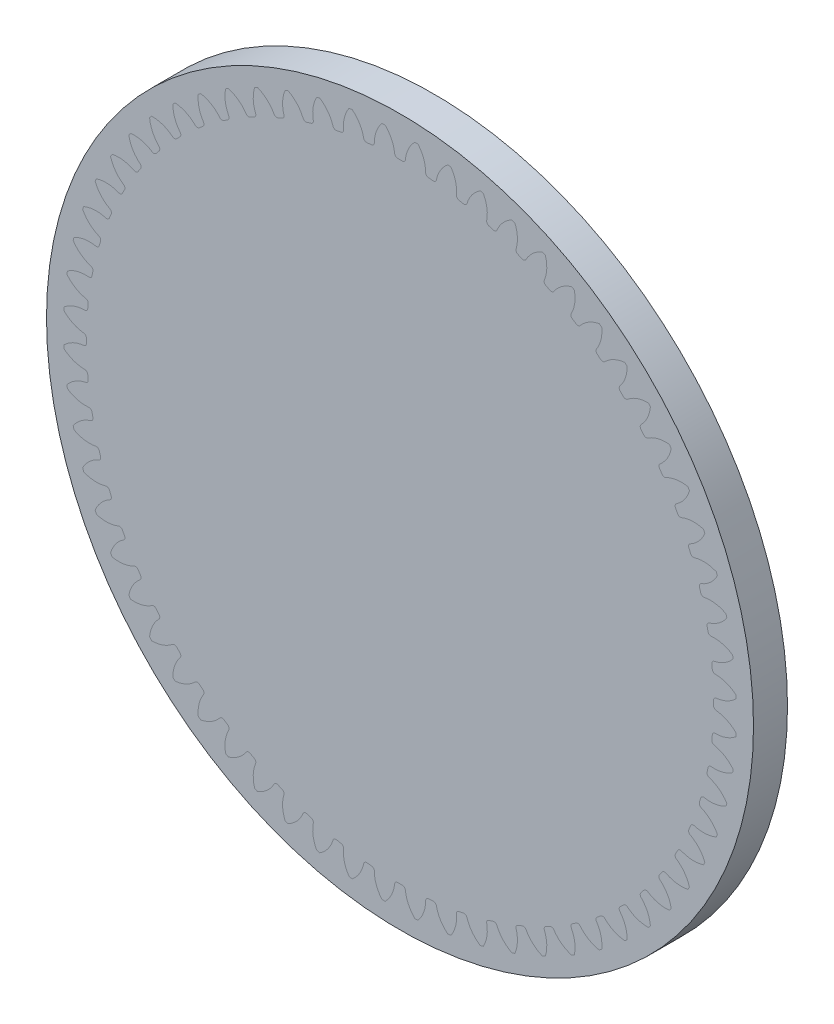
SolidWorks part; units mm, degrees
material "6061-T6 (SS)"
ref_plane "Front Plane" through (0, 0, 0) normal (0, 0, 1) x (1, 0, 0)
ref_plane "Top Plane" through (0, 0, 0) normal (0, 1, 0) x (1, 0, 0)
ref_plane "Right Plane" through (0, 0, 0) normal (1, 0, 0) x (0, 0, -1)
sketch "Sketch1" plane through (0, 0, 0) normal (0, 0, 1) x (1, 0, 0)
  circle A0 centre (0, 0) radius 96
  circle A1 centre (0, 0) radius 99
  circle A2 centre (0, 0) radius 92.25
  dimension "D1" = 192
  dimension "D2" = 198
  dimension "D3" = 6.75
extrude "Boss-Extrude1" add sketch "Sketch1" along normal mid plane 10 contours A1
sketch "Sketch2" plane through (0, 0, 0) normal (0, 0, 1) x (1, 0, 0)
  line L0 (0, 0) -> (0, 99) construction
  line L1 (-2.356, 95.9711) -> (2.356, 95.9711) construction
  line L2 (-1.5299, 92.2373) -> (0, 0) construction
  line L3 (0, 90.6795) -> (-4.1121, 99.9154) construction
  line L4 (0, 0) -> (4.8577, 98.8808) construction
  line L5 (2.356, 95.9711) -> (7.0622, 95.7399) construction
  circle A0 centre (0, 0) radius 99 construction
  arc A1 (-5.511, 99.848) -> (-1.5299, 92.2373) centre (-11.0986, 92.0786) cw
  arc A2 (5.511, 99.848) -> (1.5299, 92.2373) centre (11.0986, 92.0786) ccw
  circle A3 centre (0, 0) radius 92.25 construction
  arc A4 (1.5299, 92.2373) -> (-1.5299, 92.2373) centre (0, 0) ccw
  circle A6 centre (0, 0) radius 96 construction
  circle A7 centre (0, 0) radius 100
  arc A8 (5.511, 99.848) -> (-5.511, 99.848) centre (0, 0) ccw
  circle A9 centre (0, 0) radius 99 construction
  dimension "D2" = 24
  dimension "D3" = 2.813
extrude "Cut-Extrude1" cut sketch "Sketch2" against normal through all both and the other way through all
fillet "Fillet1" radius 0.9 2 edges at (1.5299, 92.2373, 0) (-1.5299, 92.2373, 0)
pattern_circular "CirPattern1" count 64 over 360 about axis through (0, 0, 5) along (0, 0, 1) of "Cut-Extrude1", "Fillet1"
sketch "Sketch3" plane through (0, 0, 0) normal (0, 0, 1) x (1, 0, 0)
  circle A3 centre (0, 0) radius 104
  circle A4 centre (0, 0) radius 104
  arc A388 (-5.3262, 98.8566) -> (-7.5501, 92.7623) centre (2.0199, 92.7231) ccw
  arc A389 (-8.3684, 91.8696) -> (-7.5501, 92.7623) centre (-8.4501, 92.7659) ccw
  arc A390 (-8.3684, 91.8696) -> (-9.7153, 91.737) centre (0, 0) ccw
  arc A391 (-10.692, 92.4528) -> (-9.7153, 91.737) centre (-9.8101, 92.632) ccw
  arc A392 (-10.692, 92.4528) -> (-14.0621, 97.9962) centre (-20.0705, 90.5474) ccw
  arc A393 (-14.0621, 97.9962) -> (-14.9902, 97.8585) centre (0, 0) ccw
  arc A394 (-14.9902, 97.8585) -> (-16.606, 91.5755) centre (-7.0783, 92.4746) ccw
  arc A395 (-17.3329, 90.607) -> (-16.606, 91.5755) centre (-17.502, 91.491) ccw
  arc A396 (-17.3329, 90.607) -> (-18.6603, 90.343) centre (0, 0) ccw
  arc A397 (-19.7025, 90.9596) -> (-18.6603, 90.343) centre (-18.8423, 91.2244) ccw
  arc A398 (-19.7025, 90.9596) -> (-23.5997, 96.146) centre (-28.849, 88.1441) ccw
  arc A399 (-23.5997, 96.146) -> (-24.5098, 95.918) centre (0, 0) ccw
  arc A400 (-24.5098, 95.918) -> (-25.502, 89.5069) centre (-16.1083, 91.3355) ccw
  arc A401 (-26.1305, 88.4718) -> (-25.502, 89.5069) centre (-26.3854, 89.3349) ccw
  arc A402 (-26.1305, 88.4718) -> (-27.4256, 88.0789) centre (0, 0) ccw
  arc A403 (-28.5232, 88.5904) -> (-27.4256, 88.0789) centre (-27.6932, 88.9382) ccw
  arc A404 (-28.5232, 88.5904) -> (-32.91, 93.3699) centre (-37.3497, 84.892) ccw
  arc A405 (-32.91, 93.3699) -> (-33.7934, 93.0538) centre (0, 0) ccw
  arc A406 (-33.7934, 93.0538) -> (-34.1524, 86.5763) centre (-24.9832, 89.3168) ccw
  arc A407 (-34.6764, 85.4846) -> (-34.1524, 86.5763) centre (-35.0147, 86.3185) ccw
  arc A408 (-34.6764, 85.4846) -> (-35.9268, 84.9666) centre (0, 0) ccw
  arc A409 (-37.0693, 85.3681) -> (-35.9268, 84.9666) centre (-36.2773, 85.7956) ccw
  arc A410 (-37.0693, 85.3681) -> (-41.9034, 89.6945) centre (-45.4907, 80.8223) ccw
  arc A411 (-41.9034, 89.6945) -> (-42.7516, 89.2934) centre (0, 0) ccw
  arc A412 (-42.7516, 89.2934) -> (-42.4739, 82.8119) centre (-33.6174, 86.4379) ccw
  arc A413 (-42.8884, 81.674) -> (-42.4739, 82.8119) centre (-43.3068, 82.4709) ccw
  arc A414 (-42.8884, 81.674) -> (-44.082, 81.0361) centre (0, 0) ccw
  arc A415 (-45.2583, 81.3236) -> (-44.082, 81.0361) centre (-44.512, 81.8267) ccw
  arc A416 (-45.2583, 81.3236) -> (-50.4932, 85.1554) centre (-53.1937, 75.9742) ccw
  arc A417 (-50.4932, 85.1554) -> (-51.298, 84.673) centre (0, 0) ccw
  arc A418 (-51.298, 84.673) -> (-50.3864, 78.2499) centre (-41.928, 82.7266) ccw
  arc A419 (-50.6873, 77.077) -> (-50.3864, 78.2499) centre (-51.1818, 77.8289) ccw
  arc A420 (-50.6873, 77.077) -> (-51.8126, 76.3251) centre (0, 0) ccw
  arc A421 (-53.0115, 76.4959) -> (-51.8126, 76.3251) centre (-52.3181, 77.0697) ccw
  arc A422 (-53.0115, 76.4959) -> (-58.5968, 79.7961) centre (-60.3843, 70.3945) ccw
  arc A423 (-58.5968, 79.7961) -> (-59.3504, 79.2372) centre (0, 0) ccw
  arc A424 (-59.3504, 79.2372) -> (-57.8136, 72.9344) centre (-49.8347, 78.2186) ccw
  arc A425 (-57.9981, 71.7376) -> (-57.8136, 72.9344) centre (-58.564, 72.4375) ccw
  arc A426 (-57.9981, 71.7376) -> (-59.0443, 70.879) centre (0, 0) ccw
  arc A427 (-60.2541, 70.9315) -> (-59.0443, 70.879) centre (-59.6203, 71.5705) ccw
  arc A428 (-60.2541, 70.9315) -> (-66.136, 73.6684) centre (-66.9934, 64.1368) ccw
  arc A429 (-66.136, 73.6684) -> (-66.8312, 73.0383) centre (0, 0) ccw
  arc A430 (-66.8312, 73.0383) -> (-64.684, 66.9165) centre (-57.2615, 72.9573) ccw
  arc A431 (-64.7504, 65.7073) -> (-64.684, 66.9165) centre (-65.3821, 66.3484) ccw
  arc A432 (-64.7504, 65.7073) -> (-65.7073, 64.7504) centre (0, 0) ccw
  arc A433 (-66.9165, 64.684) -> (-65.7073, 64.7504) centre (-66.3484, 65.3821) ccw
  arc A434 (-66.9165, 64.684) -> (-73.0383, 66.8312) centre (-72.9573, 57.2615) ccw
  arc A435 (-73.0383, 66.8312) -> (-73.6684, 66.136) centre (0, 0) ccw
  arc A436 (-73.6684, 66.136) -> (-70.9315, 60.2541) centre (-64.1368, 66.9934) ccw
  arc A437 (-70.879, 59.0443) -> (-70.9315, 60.2541) centre (-71.5705, 59.6203) ccw
  arc A438 (-70.879, 59.0443) -> (-71.7376, 57.9981) centre (0, 0) ccw
  arc A439 (-72.9344, 57.8136) -> (-71.7376, 57.9981) centre (-72.4375, 58.564) ccw
  arc A440 (-72.9344, 57.8136) -> (-79.2372, 59.3504) centre (-78.2186, 49.8347) ccw
  arc A441 (-79.2372, 59.3504) -> (-79.7961, 58.5968) centre (0, 0) ccw
  arc A442 (-79.7961, 58.5968) -> (-76.4959, 53.0115) centre (-70.3945, 60.3843) ccw
  arc A443 (-76.3251, 51.8126) -> (-76.4959, 53.0115) centre (-77.0697, 52.3181) ccw
  arc A444 (-76.3251, 51.8126) -> (-77.077, 50.6873) centre (0, 0) ccw
  arc A445 (-78.2499, 50.3864) -> (-77.077, 50.6873) centre (-77.8289, 51.1818) ccw
  arc A446 (-78.2499, 50.3864) -> (-84.673, 51.298) centre (-82.7266, 41.928) ccw
  arc A447 (-84.673, 51.298) -> (-85.1554, 50.4932) centre (0, 0) ccw
  arc A448 (-85.1554, 50.4932) -> (-81.3236, 45.2583) centre (-75.9742, 53.1937) ccw
  arc A449 (-81.0361, 44.082) -> (-81.3236, 45.2583) centre (-81.8267, 44.512) ccw
  arc A450 (-81.0361, 44.082) -> (-81.674, 42.8884) centre (0, 0) ccw
  arc A451 (-82.8119, 42.4739) -> (-81.674, 42.8884) centre (-82.4709, 43.3068) ccw
  arc A452 (-82.8119, 42.4739) -> (-89.2934, 42.7516) centre (-86.4379, 33.6174) ccw
  arc A453 (-89.2934, 42.7516) -> (-89.6945, 41.9034) centre (0, 0) ccw
  arc A454 (-89.6945, 41.9034) -> (-85.3681, 37.0693) centre (-80.8223, 45.4907) ccw
  arc A455 (-84.9666, 35.9268) -> (-85.3681, 37.0693) centre (-85.7956, 36.2773) ccw
  arc A456 (-84.9666, 35.9268) -> (-85.4846, 34.6764) centre (0, 0) ccw
  arc A457 (-86.5763, 34.1524) -> (-85.4846, 34.6764) centre (-86.3185, 35.0147) ccw
  arc A458 (-86.5763, 34.1524) -> (-93.0538, 33.7934) centre (-89.3168, 24.9832) ccw
  arc A459 (-93.0538, 33.7934) -> (-93.3699, 32.91) centre (0, 0) ccw
  arc A460 (-93.3699, 32.91) -> (-88.5904, 28.5232) centre (-84.892, 37.3497) ccw
  arc A461 (-88.0789, 27.4256) -> (-88.5904, 28.5232) centre (-88.9382, 27.6932) ccw
  arc A462 (-88.0789, 27.4256) -> (-88.4718, 26.1305) centre (0, 0) ccw
  arc A463 (-89.5069, 25.502) -> (-88.4718, 26.1305) centre (-89.3349, 26.3854) ccw
  arc A464 (-89.5069, 25.502) -> (-95.918, 24.5098) centre (-91.3355, 16.1083) ccw
  arc A465 (-95.918, 24.5098) -> (-96.146, 23.5997) centre (0, 0) ccw
  arc A466 (-96.146, 23.5997) -> (-90.9596, 19.7025) centre (-88.1441, 28.849) ccw
  arc A467 (-90.343, 18.6603) -> (-90.9596, 19.7025) centre (-91.2244, 18.8423) ccw
  arc A468 (-90.343, 18.6603) -> (-90.607, 17.3329) centre (0, 0) ccw
  arc A469 (-91.5755, 16.606) -> (-90.607, 17.3329) centre (-91.491, 17.502) ccw
  arc A470 (-91.5755, 16.606) -> (-97.8585, 14.9902) centre (-92.4746, 7.0783) ccw
  arc A471 (-97.8585, 14.9902) -> (-97.9962, 14.0621) centre (0, 0) ccw
  arc A472 (-97.9962, 14.0621) -> (-92.4528, 10.692) centre (-90.5474, 20.0705) ccw
  arc A473 (-91.737, 9.7153) -> (-92.4528, 10.692) centre (-92.632, 9.8101) ccw
  arc A474 (-91.737, 9.7153) -> (-91.8696, 8.3684) centre (0, 0) ccw
  arc A475 (-92.7623, 7.5501) -> (-91.8696, 8.3684) centre (-92.7659, 8.4501) ccw
  arc A476 (-92.7623, 7.5501) -> (-98.8566, 5.3262) centre (-92.7231, -2.0199) ccw
  arc A477 (-98.8566, 5.3262) -> (-98.9027, 4.3891) centre (0, 0) ccw
  arc A478 (-98.9027, 4.3891) -> (-93.0556, 1.5786) centre (-92.0786, 11.0986) ccw
  arc A479 (-92.2475, 0.6767) -> (-93.0556, 1.5786) centre (-93.1475, 0.6833) ccw
  arc A480 (-92.2475, 0.6767) -> (-92.2475, -0.6767) centre (0, 0) ccw
  arc A481 (-93.0556, -1.5786) -> (-92.2475, -0.6767) centre (-93.1475, -0.6833) ccw
  arc A482 (-93.0556, -1.5786) -> (-98.9027, -4.3891) centre (-92.0786, -11.0986) ccw
  arc A483 (-98.9027, -4.3891) -> (-98.8566, -5.3262) centre (0, 0) ccw
  arc A484 (-98.8566, -5.3262) -> (-92.7623, -7.5501) centre (-92.7231, 2.0199) ccw
  arc A485 (-91.8696, -8.3684) -> (-92.7623, -7.5501) centre (-92.7659, -8.4501) ccw
  arc A486 (-91.8696, -8.3684) -> (-91.737, -9.7153) centre (0, 0) ccw
  arc A487 (-92.4528, -10.692) -> (-91.737, -9.7153) centre (-92.632, -9.8101) ccw
  arc A488 (-92.4528, -10.692) -> (-97.9962, -14.0621) centre (-90.5474, -20.0705) ccw
  arc A489 (-97.9962, -14.0621) -> (-97.8585, -14.9902) centre (0, 0) ccw
  arc A490 (-97.8585, -14.9902) -> (-91.5755, -16.606) centre (-92.4746, -7.0783) ccw
  arc A491 (-90.607, -17.3329) -> (-91.5755, -16.606) centre (-91.491, -17.502) ccw
  arc A492 (-90.607, -17.3329) -> (-90.343, -18.6603) centre (0, 0) ccw
  arc A493 (-90.9596, -19.7025) -> (-90.343, -18.6603) centre (-91.2244, -18.8423) ccw
  arc A494 (-90.9596, -19.7025) -> (-96.146, -23.5997) centre (-88.1441, -28.849) ccw
  arc A495 (-96.146, -23.5997) -> (-95.918, -24.5098) centre (0, 0) ccw
  arc A496 (-95.918, -24.5098) -> (-89.5069, -25.502) centre (-91.3355, -16.1083) ccw
  arc A497 (-88.4718, -26.1305) -> (-89.5069, -25.502) centre (-89.3349, -26.3854) ccw
  arc A498 (-88.4718, -26.1305) -> (-88.0789, -27.4256) centre (0, 0) ccw
  arc A499 (-88.5904, -28.5232) -> (-88.0789, -27.4256) centre (-88.9382, -27.6932) ccw
  arc A500 (-88.5904, -28.5232) -> (-93.3699, -32.91) centre (-84.892, -37.3497) ccw
  arc A501 (-93.3699, -32.91) -> (-93.0538, -33.7934) centre (0, 0) ccw
  arc A502 (-93.0538, -33.7934) -> (-86.5763, -34.1524) centre (-89.3168, -24.9832) ccw
  arc A503 (-85.4846, -34.6764) -> (-86.5763, -34.1524) centre (-86.3185, -35.0147) ccw
  arc A504 (-85.4846, -34.6764) -> (-84.9666, -35.9268) centre (0, 0) ccw
  arc A505 (-85.3681, -37.0693) -> (-84.9666, -35.9268) centre (-85.7956, -36.2773) ccw
  arc A506 (-85.3681, -37.0693) -> (-89.6945, -41.9034) centre (-80.8223, -45.4907) ccw
  arc A507 (-89.6945, -41.9034) -> (-89.2934, -42.7516) centre (0, 0) ccw
  arc A508 (-89.2934, -42.7516) -> (-82.8119, -42.4739) centre (-86.4379, -33.6174) ccw
  arc A509 (-81.674, -42.8884) -> (-82.8119, -42.4739) centre (-82.4709, -43.3068) ccw
  arc A510 (-81.674, -42.8884) -> (-81.0361, -44.082) centre (0, 0) ccw
  arc A511 (-81.3236, -45.2583) -> (-81.0361, -44.082) centre (-81.8267, -44.512) ccw
  arc A512 (-81.3236, -45.2583) -> (-85.1554, -50.4932) centre (-75.9742, -53.1937) ccw
  arc A513 (-85.1554, -50.4932) -> (-84.673, -51.298) centre (0, 0) ccw
  arc A514 (-84.673, -51.298) -> (-78.2499, -50.3864) centre (-82.7266, -41.928) ccw
  arc A515 (-77.077, -50.6873) -> (-78.2499, -50.3864) centre (-77.8289, -51.1818) ccw
  arc A516 (-77.077, -50.6873) -> (-76.3251, -51.8126) centre (0, 0) ccw
  arc A517 (-76.4959, -53.0115) -> (-76.3251, -51.8126) centre (-77.0697, -52.3181) ccw
  arc A518 (-76.4959, -53.0115) -> (-79.7961, -58.5968) centre (-70.3945, -60.3843) ccw
  arc A519 (-79.7961, -58.5968) -> (-79.2372, -59.3504) centre (0, 0) ccw
  arc A520 (-79.2372, -59.3504) -> (-72.9344, -57.8136) centre (-78.2186, -49.8347) ccw
  arc A521 (-71.7376, -57.9981) -> (-72.9344, -57.8136) centre (-72.4375, -58.564) ccw
  arc A522 (-71.7376, -57.9981) -> (-70.879, -59.0443) centre (0, 0) ccw
  arc A523 (-70.9315, -60.2541) -> (-70.879, -59.0443) centre (-71.5705, -59.6203) ccw
  arc A524 (-70.9315, -60.2541) -> (-73.6684, -66.136) centre (-64.1368, -66.9934) ccw
  arc A525 (-73.6684, -66.136) -> (-73.0383, -66.8312) centre (0, 0) ccw
  arc A526 (-73.0383, -66.8312) -> (-66.9165, -64.684) centre (-72.9573, -57.2615) ccw
  arc A527 (-65.7073, -64.7504) -> (-66.9165, -64.684) centre (-66.3484, -65.3821) ccw
  arc A528 (-65.7073, -64.7504) -> (-64.7504, -65.7073) centre (0, 0) ccw
  arc A529 (-64.684, -66.9165) -> (-64.7504, -65.7073) centre (-65.3821, -66.3484) ccw
  arc A530 (-64.684, -66.9165) -> (-66.8312, -73.0383) centre (-57.2615, -72.9573) ccw
  arc A531 (-66.8312, -73.0383) -> (-66.136, -73.6684) centre (0, 0) ccw
  arc A532 (-66.136, -73.6684) -> (-60.2541, -70.9315) centre (-66.9934, -64.1368) ccw
  arc A533 (-59.0443, -70.879) -> (-60.2541, -70.9315) centre (-59.6203, -71.5705) ccw
  arc A534 (-59.0443, -70.879) -> (-57.9981, -71.7376) centre (0, 0) ccw
  arc A535 (-57.8136, -72.9344) -> (-57.9981, -71.7376) centre (-58.564, -72.4375) ccw
  arc A536 (-57.8136, -72.9344) -> (-59.3504, -79.2372) centre (-49.8347, -78.2186) ccw
  arc A537 (-59.3504, -79.2372) -> (-58.5968, -79.7961) centre (0, 0) ccw
  arc A538 (-58.5968, -79.7961) -> (-53.0115, -76.4959) centre (-60.3843, -70.3945) ccw
  arc A539 (-51.8126, -76.3251) -> (-53.0115, -76.4959) centre (-52.3181, -77.0697) ccw
  arc A540 (-51.8126, -76.3251) -> (-50.6873, -77.077) centre (0, 0) ccw
  arc A541 (-50.3864, -78.2499) -> (-50.6873, -77.077) centre (-51.1818, -77.8289) ccw
  arc A542 (-50.3864, -78.2499) -> (-51.298, -84.673) centre (-41.928, -82.7266) ccw
  arc A543 (-51.298, -84.673) -> (-50.4932, -85.1554) centre (0, 0) ccw
  arc A544 (-50.4932, -85.1554) -> (-45.2583, -81.3236) centre (-53.1937, -75.9742) ccw
  arc A545 (-44.082, -81.0361) -> (-45.2583, -81.3236) centre (-44.512, -81.8267) ccw
  arc A546 (-44.082, -81.0361) -> (-42.8884, -81.674) centre (0, 0) ccw
  arc A547 (-42.4739, -82.8119) -> (-42.8884, -81.674) centre (-43.3068, -82.4709) ccw
  arc A548 (-42.4739, -82.8119) -> (-42.7516, -89.2934) centre (-33.6174, -86.4379) ccw
  arc A549 (-42.7516, -89.2934) -> (-41.9034, -89.6945) centre (0, 0) ccw
  arc A550 (-41.9034, -89.6945) -> (-37.0693, -85.3681) centre (-45.4907, -80.8223) ccw
  arc A551 (-35.9268, -84.9666) -> (-37.0693, -85.3681) centre (-36.2773, -85.7956) ccw
  arc A552 (-35.9268, -84.9666) -> (-34.6764, -85.4846) centre (0, 0) ccw
  arc A553 (-34.1524, -86.5763) -> (-34.6764, -85.4846) centre (-35.0147, -86.3185) ccw
  arc A554 (-34.1524, -86.5763) -> (-33.7934, -93.0538) centre (-24.9832, -89.3168) ccw
  arc A555 (-33.7934, -93.0538) -> (-32.91, -93.3699) centre (0, 0) ccw
  arc A556 (-32.91, -93.3699) -> (-28.5232, -88.5904) centre (-37.3497, -84.892) ccw
  arc A557 (-27.4256, -88.0789) -> (-28.5232, -88.5904) centre (-27.6932, -88.9382) ccw
  arc A558 (-27.4256, -88.0789) -> (-26.1305, -88.4718) centre (0, 0) ccw
  arc A559 (-25.502, -89.5069) -> (-26.1305, -88.4718) centre (-26.3854, -89.3349) ccw
  arc A560 (-25.502, -89.5069) -> (-24.5098, -95.918) centre (-16.1083, -91.3355) ccw
  arc A561 (-24.5098, -95.918) -> (-23.5997, -96.146) centre (0, 0) ccw
  arc A562 (-23.5997, -96.146) -> (-19.7025, -90.9596) centre (-28.849, -88.1441) ccw
  arc A563 (-18.6603, -90.343) -> (-19.7025, -90.9596) centre (-18.8423, -91.2244) ccw
  arc A564 (-18.6603, -90.343) -> (-17.3329, -90.607) centre (0, 0) ccw
  arc A565 (-16.606, -91.5755) -> (-17.3329, -90.607) centre (-17.502, -91.491) ccw
  arc A566 (-16.606, -91.5755) -> (-14.9902, -97.8585) centre (-7.0783, -92.4746) ccw
  arc A567 (-14.9902, -97.8585) -> (-14.0621, -97.9962) centre (0, 0) ccw
  arc A568 (-14.0621, -97.9962) -> (-10.692, -92.4528) centre (-20.0705, -90.5474) ccw
  arc A569 (-9.7153, -91.737) -> (-10.692, -92.4528) centre (-9.8101, -92.632) ccw
  arc A570 (-9.7153, -91.737) -> (-8.3684, -91.8696) centre (0, 0) ccw
  arc A571 (-7.5501, -92.7623) -> (-8.3684, -91.8696) centre (-8.4501, -92.7659) ccw
  arc A572 (-7.5501, -92.7623) -> (-5.3262, -98.8566) centre (2.0199, -92.7231) ccw
  arc A573 (-5.3262, -98.8566) -> (-4.3891, -98.9027) centre (0, 0) ccw
  arc A574 (-4.3891, -98.9027) -> (-1.5786, -93.0556) centre (-11.0986, -92.0786) ccw
  arc A575 (-0.6767, -92.2475) -> (-1.5786, -93.0556) centre (-0.6833, -93.1475) ccw
  arc A576 (-0.6767, -92.2475) -> (0.6767, -92.2475) centre (0, 0) ccw
  arc A577 (1.5786, -93.0556) -> (0.6767, -92.2475) centre (0.6833, -93.1475) ccw
  arc A578 (1.5786, -93.0556) -> (4.3891, -98.9027) centre (11.0986, -92.0786) ccw
  arc A579 (4.3891, -98.9027) -> (5.3262, -98.8566) centre (0, 0) ccw
  arc A580 (5.3262, -98.8566) -> (7.5501, -92.7623) centre (-2.0199, -92.7231) ccw
  arc A581 (8.3684, -91.8696) -> (7.5501, -92.7623) centre (8.4501, -92.7659) ccw
  arc A582 (8.3684, -91.8696) -> (9.7153, -91.737) centre (0, 0) ccw
  arc A583 (10.692, -92.4528) -> (9.7153, -91.737) centre (9.8101, -92.632) ccw
  arc A584 (10.692, -92.4528) -> (14.0621, -97.9962) centre (20.0705, -90.5474) ccw
  arc A585 (14.0621, -97.9962) -> (14.9902, -97.8585) centre (0, 0) ccw
  arc A586 (14.9902, -97.8585) -> (16.606, -91.5755) centre (7.0783, -92.4746) ccw
  arc A587 (17.3329, -90.607) -> (16.606, -91.5755) centre (17.502, -91.491) ccw
  arc A588 (17.3329, -90.607) -> (18.6603, -90.343) centre (0, 0) ccw
  arc A589 (19.7025, -90.9596) -> (18.6603, -90.343) centre (18.8423, -91.2244) ccw
  arc A590 (19.7025, -90.9596) -> (23.5997, -96.146) centre (28.849, -88.1441) ccw
  arc A591 (23.5997, -96.146) -> (24.5098, -95.918) centre (0, 0) ccw
  arc A592 (24.5098, -95.918) -> (25.502, -89.5069) centre (16.1083, -91.3355) ccw
  arc A593 (26.1305, -88.4718) -> (25.502, -89.5069) centre (26.3854, -89.3349) ccw
  arc A594 (26.1305, -88.4718) -> (27.4256, -88.0789) centre (0, 0) ccw
  arc A595 (28.5232, -88.5904) -> (27.4256, -88.0789) centre (27.6932, -88.9382) ccw
  arc A596 (28.5232, -88.5904) -> (32.91, -93.3699) centre (37.3497, -84.892) ccw
  arc A597 (32.91, -93.3699) -> (33.7934, -93.0538) centre (0, 0) ccw
  arc A598 (33.7934, -93.0538) -> (34.1524, -86.5763) centre (24.9832, -89.3168) ccw
  arc A599 (34.6764, -85.4846) -> (34.1524, -86.5763) centre (35.0147, -86.3185) ccw
  arc A600 (34.6764, -85.4846) -> (35.9268, -84.9666) centre (0, 0) ccw
  arc A601 (37.0693, -85.3681) -> (35.9268, -84.9666) centre (36.2773, -85.7956) ccw
  arc A602 (37.0693, -85.3681) -> (41.9034, -89.6945) centre (45.4907, -80.8223) ccw
  arc A603 (41.9034, -89.6945) -> (42.7516, -89.2934) centre (0, 0) ccw
  arc A604 (42.7516, -89.2934) -> (42.4739, -82.8119) centre (33.6174, -86.4379) ccw
  arc A605 (42.8884, -81.674) -> (42.4739, -82.8119) centre (43.3068, -82.4709) ccw
  arc A606 (42.8884, -81.674) -> (44.082, -81.0361) centre (0, 0) ccw
  arc A607 (45.2583, -81.3236) -> (44.082, -81.0361) centre (44.512, -81.8267) ccw
  arc A608 (45.2583, -81.3236) -> (50.4932, -85.1554) centre (53.1937, -75.9742) ccw
  arc A609 (50.4932, -85.1554) -> (51.298, -84.673) centre (0, 0) ccw
  arc A610 (51.298, -84.673) -> (50.3864, -78.2499) centre (41.928, -82.7266) ccw
  arc A611 (50.6873, -77.077) -> (50.3864, -78.2499) centre (51.1818, -77.8289) ccw
  arc A612 (50.6873, -77.077) -> (51.8126, -76.3251) centre (0, 0) ccw
  arc A613 (53.0115, -76.4959) -> (51.8126, -76.3251) centre (52.3181, -77.0697) ccw
  arc A614 (53.0115, -76.4959) -> (58.5968, -79.7961) centre (60.3843, -70.3945) ccw
  arc A615 (58.5968, -79.7961) -> (59.3504, -79.2372) centre (0, 0) ccw
  arc A616 (59.3504, -79.2372) -> (57.8136, -72.9344) centre (49.8347, -78.2186) ccw
  arc A617 (57.9981, -71.7376) -> (57.8136, -72.9344) centre (58.564, -72.4375) ccw
  arc A618 (57.9981, -71.7376) -> (59.0443, -70.879) centre (0, 0) ccw
  arc A619 (60.2541, -70.9315) -> (59.0443, -70.879) centre (59.6203, -71.5705) ccw
  arc A620 (60.2541, -70.9315) -> (66.136, -73.6684) centre (66.9934, -64.1368) ccw
  arc A621 (66.136, -73.6684) -> (66.8312, -73.0383) centre (0, 0) ccw
  arc A622 (66.8312, -73.0383) -> (64.684, -66.9165) centre (57.2615, -72.9573) ccw
  arc A623 (64.7504, -65.7073) -> (64.684, -66.9165) centre (65.3821, -66.3484) ccw
  arc A624 (64.7504, -65.7073) -> (65.7073, -64.7504) centre (0, 0) ccw
  arc A625 (66.9165, -64.684) -> (65.7073, -64.7504) centre (66.3484, -65.3821) ccw
  arc A626 (66.9165, -64.684) -> (73.0383, -66.8312) centre (72.9573, -57.2615) ccw
  arc A627 (73.0383, -66.8312) -> (73.6684, -66.136) centre (0, 0) ccw
  arc A628 (73.6684, -66.136) -> (70.9315, -60.2541) centre (64.1368, -66.9934) ccw
  arc A629 (70.879, -59.0443) -> (70.9315, -60.2541) centre (71.5705, -59.6203) ccw
  arc A630 (70.879, -59.0443) -> (71.7376, -57.9981) centre (0, 0) ccw
  arc A631 (72.9344, -57.8136) -> (71.7376, -57.9981) centre (72.4375, -58.564) ccw
  arc A632 (72.9344, -57.8136) -> (79.2372, -59.3504) centre (78.2186, -49.8347) ccw
  arc A633 (79.2372, -59.3504) -> (79.7961, -58.5968) centre (0, 0) ccw
  arc A634 (79.7961, -58.5968) -> (76.4959, -53.0115) centre (70.3945, -60.3843) ccw
  arc A635 (76.3251, -51.8126) -> (76.4959, -53.0115) centre (77.0697, -52.3181) ccw
  arc A636 (76.3251, -51.8126) -> (77.077, -50.6873) centre (0, 0) ccw
  arc A637 (78.2499, -50.3864) -> (77.077, -50.6873) centre (77.8289, -51.1818) ccw
  arc A638 (78.2499, -50.3864) -> (84.673, -51.298) centre (82.7266, -41.928) ccw
  arc A639 (84.673, -51.298) -> (85.1554, -50.4932) centre (0, 0) ccw
  arc A640 (85.1554, -50.4932) -> (81.3236, -45.2583) centre (75.9742, -53.1937) ccw
  arc A641 (81.0361, -44.082) -> (81.3236, -45.2583) centre (81.8267, -44.512) ccw
  arc A642 (81.0361, -44.082) -> (81.674, -42.8884) centre (0, 0) ccw
  arc A643 (82.8119, -42.4739) -> (81.674, -42.8884) centre (82.4709, -43.3068) ccw
  arc A644 (82.8119, -42.4739) -> (89.2934, -42.7516) centre (86.4379, -33.6174) ccw
  arc A645 (89.2934, -42.7516) -> (89.6945, -41.9034) centre (0, 0) ccw
  arc A646 (89.6945, -41.9034) -> (85.3681, -37.0693) centre (80.8223, -45.4907) ccw
  arc A647 (84.9666, -35.9268) -> (85.3681, -37.0693) centre (85.7956, -36.2773) ccw
  arc A648 (84.9666, -35.9268) -> (85.4846, -34.6764) centre (0, 0) ccw
  arc A649 (86.5763, -34.1524) -> (85.4846, -34.6764) centre (86.3185, -35.0147) ccw
  arc A650 (86.5763, -34.1524) -> (93.0538, -33.7934) centre (89.3168, -24.9832) ccw
  arc A651 (93.0538, -33.7934) -> (93.3699, -32.91) centre (0, 0) ccw
  arc A652 (93.3699, -32.91) -> (88.5904, -28.5232) centre (84.892, -37.3497) ccw
  arc A653 (88.0789, -27.4256) -> (88.5904, -28.5232) centre (88.9382, -27.6932) ccw
  arc A654 (88.0789, -27.4256) -> (88.4718, -26.1305) centre (0, 0) ccw
  arc A655 (89.5069, -25.502) -> (88.4718, -26.1305) centre (89.3349, -26.3854) ccw
  arc A656 (89.5069, -25.502) -> (95.918, -24.5098) centre (91.3355, -16.1083) ccw
  arc A657 (95.918, -24.5098) -> (96.146, -23.5997) centre (0, 0) ccw
  arc A658 (96.146, -23.5997) -> (90.9596, -19.7025) centre (88.1441, -28.849) ccw
  arc A659 (90.343, -18.6603) -> (90.9596, -19.7025) centre (91.2244, -18.8423) ccw
  arc A660 (90.343, -18.6603) -> (90.607, -17.3329) centre (0, 0) ccw
  arc A661 (91.5755, -16.606) -> (90.607, -17.3329) centre (91.491, -17.502) ccw
  arc A662 (91.5755, -16.606) -> (97.8585, -14.9902) centre (92.4746, -7.0783) ccw
  arc A663 (97.8585, -14.9902) -> (97.9962, -14.0621) centre (0, 0) ccw
  arc A664 (97.9962, -14.0621) -> (92.4528, -10.692) centre (90.5474, -20.0705) ccw
  arc A665 (91.737, -9.7153) -> (92.4528, -10.692) centre (92.632, -9.8101) ccw
  arc A666 (91.737, -9.7153) -> (91.8696, -8.3684) centre (0, 0) ccw
  arc A667 (92.7623, -7.5501) -> (91.8696, -8.3684) centre (92.7659, -8.4501) ccw
  arc A668 (92.7623, -7.5501) -> (98.8566, -5.3262) centre (92.7231, 2.0199) ccw
  arc A669 (98.8566, -5.3262) -> (98.9027, -4.3891) centre (0, 0) ccw
  arc A670 (98.9027, -4.3891) -> (93.0556, -1.5786) centre (92.0786, -11.0986) ccw
  arc A671 (92.2475, -0.6767) -> (93.0556, -1.5786) centre (93.1475, -0.6833) ccw
  arc A672 (92.2475, -0.6767) -> (92.2475, 0.6767) centre (0, 0) ccw
  arc A673 (93.0556, 1.5786) -> (92.2475, 0.6767) centre (93.1475, 0.6833) ccw
  arc A674 (93.0556, 1.5786) -> (98.9027, 4.3891) centre (92.0786, 11.0986) ccw
  arc A675 (98.9027, 4.3891) -> (98.8566, 5.3262) centre (0, 0) ccw
  arc A676 (98.8566, 5.3262) -> (92.7623, 7.5501) centre (92.7231, -2.0199) ccw
  arc A677 (91.8696, 8.3684) -> (92.7623, 7.5501) centre (92.7659, 8.4501) ccw
  arc A678 (91.8696, 8.3684) -> (91.737, 9.7153) centre (0, 0) ccw
  arc A679 (92.4528, 10.692) -> (91.737, 9.7153) centre (92.632, 9.8101) ccw
  arc A680 (92.4528, 10.692) -> (97.9962, 14.0621) centre (90.5474, 20.0705) ccw
  arc A681 (97.9962, 14.0621) -> (97.8585, 14.9902) centre (0, 0) ccw
  arc A682 (97.8585, 14.9902) -> (91.5755, 16.606) centre (92.4746, 7.0783) ccw
  arc A683 (90.607, 17.3329) -> (91.5755, 16.606) centre (91.491, 17.502) ccw
  arc A684 (90.607, 17.3329) -> (90.343, 18.6603) centre (0, 0) ccw
  arc A685 (90.9596, 19.7025) -> (90.343, 18.6603) centre (91.2244, 18.8423) ccw
  arc A686 (90.9596, 19.7025) -> (96.146, 23.5997) centre (88.1441, 28.849) ccw
  arc A687 (96.146, 23.5997) -> (95.918, 24.5098) centre (0, 0) ccw
  arc A688 (95.918, 24.5098) -> (89.5069, 25.502) centre (91.3355, 16.1083) ccw
  arc A689 (88.4718, 26.1305) -> (89.5069, 25.502) centre (89.3349, 26.3854) ccw
  arc A690 (88.4718, 26.1305) -> (88.0789, 27.4256) centre (0, 0) ccw
  arc A691 (88.5904, 28.5232) -> (88.0789, 27.4256) centre (88.9382, 27.6932) ccw
  arc A692 (88.5904, 28.5232) -> (93.3699, 32.91) centre (84.892, 37.3497) ccw
  arc A693 (93.3699, 32.91) -> (93.0538, 33.7934) centre (0, 0) ccw
  arc A694 (93.0538, 33.7934) -> (86.5763, 34.1524) centre (89.3168, 24.9832) ccw
  arc A695 (85.4846, 34.6764) -> (86.5763, 34.1524) centre (86.3185, 35.0147) ccw
  arc A696 (85.4846, 34.6764) -> (84.9666, 35.9268) centre (0, 0) ccw
  arc A697 (85.3681, 37.0693) -> (84.9666, 35.9268) centre (85.7956, 36.2773) ccw
  arc A698 (85.3681, 37.0693) -> (89.6945, 41.9034) centre (80.8223, 45.4907) ccw
  arc A699 (89.6945, 41.9034) -> (89.2934, 42.7516) centre (0, 0) ccw
  arc A700 (89.2934, 42.7516) -> (82.8119, 42.4739) centre (86.4379, 33.6174) ccw
  arc A701 (81.674, 42.8884) -> (82.8119, 42.4739) centre (82.4709, 43.3068) ccw
  arc A702 (81.674, 42.8884) -> (81.0361, 44.082) centre (0, 0) ccw
  arc A703 (81.3236, 45.2583) -> (81.0361, 44.082) centre (81.8267, 44.512) ccw
  arc A704 (81.3236, 45.2583) -> (85.1554, 50.4932) centre (75.9742, 53.1937) ccw
  arc A705 (85.1554, 50.4932) -> (84.673, 51.298) centre (0, 0) ccw
  arc A706 (84.673, 51.298) -> (78.2499, 50.3864) centre (82.7266, 41.928) ccw
  arc A707 (77.077, 50.6873) -> (78.2499, 50.3864) centre (77.8289, 51.1818) ccw
  arc A708 (77.077, 50.6873) -> (76.3251, 51.8126) centre (0, 0) ccw
  arc A709 (76.4959, 53.0115) -> (76.3251, 51.8126) centre (77.0697, 52.3181) ccw
  arc A710 (76.4959, 53.0115) -> (79.7961, 58.5968) centre (70.3945, 60.3843) ccw
  arc A711 (79.7961, 58.5968) -> (79.2372, 59.3504) centre (0, 0) ccw
  arc A712 (79.2372, 59.3504) -> (72.9344, 57.8136) centre (78.2186, 49.8347) ccw
  arc A713 (71.7376, 57.9981) -> (72.9344, 57.8136) centre (72.4375, 58.564) ccw
  arc A714 (71.7376, 57.9981) -> (70.879, 59.0443) centre (0, 0) ccw
  arc A715 (70.9315, 60.2541) -> (70.879, 59.0443) centre (71.5705, 59.6203) ccw
  arc A716 (70.9315, 60.2541) -> (73.6684, 66.136) centre (64.1368, 66.9934) ccw
  arc A717 (73.6684, 66.136) -> (73.0383, 66.8312) centre (0, 0) ccw
  arc A718 (73.0383, 66.8312) -> (66.9165, 64.684) centre (72.9573, 57.2615) ccw
  arc A719 (65.7073, 64.7504) -> (66.9165, 64.684) centre (66.3484, 65.3821) ccw
  arc A720 (65.7073, 64.7504) -> (64.7504, 65.7073) centre (0, 0) ccw
  arc A721 (64.684, 66.9165) -> (64.7504, 65.7073) centre (65.3821, 66.3484) ccw
  arc A722 (64.684, 66.9165) -> (66.8312, 73.0383) centre (57.2615, 72.9573) ccw
  arc A723 (66.8312, 73.0383) -> (66.136, 73.6684) centre (0, 0) ccw
  arc A724 (66.136, 73.6684) -> (60.2541, 70.9315) centre (66.9934, 64.1368) ccw
  arc A725 (59.0443, 70.879) -> (60.2541, 70.9315) centre (59.6203, 71.5705) ccw
  arc A726 (59.0443, 70.879) -> (57.9981, 71.7376) centre (0, 0) ccw
  arc A727 (57.8136, 72.9344) -> (57.9981, 71.7376) centre (58.564, 72.4375) ccw
  arc A728 (57.8136, 72.9344) -> (59.3504, 79.2372) centre (49.8347, 78.2186) ccw
  arc A729 (59.3504, 79.2372) -> (58.5968, 79.7961) centre (0, 0) ccw
  arc A730 (58.5968, 79.7961) -> (53.0115, 76.4959) centre (60.3843, 70.3945) ccw
  arc A731 (51.8126, 76.3251) -> (53.0115, 76.4959) centre (52.3181, 77.0697) ccw
  arc A732 (51.8126, 76.3251) -> (50.6873, 77.077) centre (0, 0) ccw
  arc A733 (50.3864, 78.2499) -> (50.6873, 77.077) centre (51.1818, 77.8289) ccw
  arc A734 (50.3864, 78.2499) -> (51.298, 84.673) centre (41.928, 82.7266) ccw
  arc A735 (51.298, 84.673) -> (50.4932, 85.1554) centre (0, 0) ccw
  arc A736 (50.4932, 85.1554) -> (45.2583, 81.3236) centre (53.1937, 75.9742) ccw
  arc A737 (44.082, 81.0361) -> (45.2583, 81.3236) centre (44.512, 81.8267) ccw
  arc A738 (44.082, 81.0361) -> (42.8884, 81.674) centre (0, 0) ccw
  arc A739 (42.4739, 82.8119) -> (42.8884, 81.674) centre (43.3068, 82.4709) ccw
  arc A740 (42.4739, 82.8119) -> (42.7516, 89.2934) centre (33.6174, 86.4379) ccw
  arc A741 (42.7516, 89.2934) -> (41.9034, 89.6945) centre (0, 0) ccw
  arc A742 (41.9034, 89.6945) -> (37.0693, 85.3681) centre (45.4907, 80.8223) ccw
  arc A743 (35.9268, 84.9666) -> (37.0693, 85.3681) centre (36.2773, 85.7956) ccw
  arc A744 (35.9268, 84.9666) -> (34.6764, 85.4846) centre (0, 0) ccw
  arc A745 (34.1524, 86.5763) -> (34.6764, 85.4846) centre (35.0147, 86.3185) ccw
  arc A746 (34.1524, 86.5763) -> (33.7934, 93.0538) centre (24.9832, 89.3168) ccw
  arc A747 (33.7934, 93.0538) -> (32.91, 93.3699) centre (0, 0) ccw
  arc A748 (32.91, 93.3699) -> (28.5232, 88.5904) centre (37.3497, 84.892) ccw
  arc A749 (27.4256, 88.0789) -> (28.5232, 88.5904) centre (27.6932, 88.9382) ccw
  arc A750 (27.4256, 88.0789) -> (26.1305, 88.4718) centre (0, 0) ccw
  arc A751 (25.502, 89.5069) -> (26.1305, 88.4718) centre (26.3854, 89.3349) ccw
  arc A752 (25.502, 89.5069) -> (24.5098, 95.918) centre (16.1083, 91.3355) ccw
  arc A753 (24.5098, 95.918) -> (23.5997, 96.146) centre (0, 0) ccw
  arc A754 (23.5997, 96.146) -> (19.7025, 90.9596) centre (28.849, 88.1441) ccw
  arc A755 (18.6603, 90.343) -> (19.7025, 90.9596) centre (18.8423, 91.2244) ccw
  arc A756 (18.6603, 90.343) -> (17.3329, 90.607) centre (0, 0) ccw
  arc A757 (16.606, 91.5755) -> (17.3329, 90.607) centre (17.502, 91.491) ccw
  arc A758 (16.606, 91.5755) -> (14.9902, 97.8585) centre (7.0783, 92.4746) ccw
  arc A759 (14.9902, 97.8585) -> (14.0621, 97.9962) centre (0, 0) ccw
  arc A760 (14.0621, 97.9962) -> (10.692, 92.4528) centre (20.0705, 90.5474) ccw
  arc A761 (9.7153, 91.737) -> (10.692, 92.4528) centre (9.8101, 92.632) ccw
  arc A762 (9.7153, 91.737) -> (8.3684, 91.8696) centre (0, 0) ccw
  arc A763 (7.5501, 92.7623) -> (8.3684, 91.8696) centre (8.4501, 92.7659) ccw
  arc A764 (7.5501, 92.7623) -> (5.3262, 98.8566) centre (-2.0199, 92.7231) ccw
  arc A765 (5.3262, 98.8566) -> (4.3891, 98.9027) centre (0, 0) ccw
  arc A766 (4.3891, 98.9027) -> (1.5786, 93.0556) centre (11.0986, 92.0786) ccw
  arc A767 (0.6767, 92.2475) -> (1.5786, 93.0556) centre (0.6833, 93.1475) ccw
  arc A768 (0.6767, 92.2475) -> (-0.6767, 92.2475) centre (0, 0) ccw
  arc A769 (-1.5786, 93.0556) -> (-0.6767, 92.2475) centre (-0.6833, 93.1475) ccw
  arc A770 (-1.5786, 93.0556) -> (-4.3891, 98.9027) centre (-11.0986, 92.0786) ccw
  arc A771 (-4.3891, 98.9027) -> (-5.3262, 98.8566) centre (0, 0) ccw
  arc A772 (-5.3262, 98.8566) -> (-7.5501, 92.7623) centre (2.0199, 92.7231) ccw
  arc A773 (-8.3684, 91.8696) -> (-7.5501, 92.7623) centre (-8.4501, 92.7659) ccw
  arc A774 (-8.3684, 91.8696) -> (-9.7153, 91.737) centre (0, 0) ccw
  arc A775 (-10.692, 92.4528) -> (-9.7153, 91.737) centre (-9.8101, 92.632) ccw
  arc A776 (-10.692, 92.4528) -> (-14.0621, 97.9962) centre (-20.0705, 90.5474) ccw
  arc A777 (-14.0621, 97.9962) -> (-14.9902, 97.8585) centre (0, 0) ccw
  arc A778 (-14.9902, 97.8585) -> (-16.606, 91.5755) centre (-7.0783, 92.4746) ccw
  arc A779 (-17.3329, 90.607) -> (-16.606, 91.5755) centre (-17.502, 91.491) ccw
  arc A780 (-17.3329, 90.607) -> (-18.6603, 90.343) centre (0, 0) ccw
  arc A781 (-19.7025, 90.9596) -> (-18.6603, 90.343) centre (-18.8423, 91.2244) ccw
  arc A782 (-19.7025, 90.9596) -> (-23.5997, 96.146) centre (-28.849, 88.1441) ccw
  arc A783 (-23.5997, 96.146) -> (-24.5098, 95.918) centre (0, 0) ccw
  arc A784 (-24.5098, 95.918) -> (-25.502, 89.5069) centre (-16.1083, 91.3355) ccw
  arc A785 (-26.1305, 88.4718) -> (-25.502, 89.5069) centre (-26.3854, 89.3349) ccw
  arc A786 (-26.1305, 88.4718) -> (-27.4256, 88.0789) centre (0, 0) ccw
  arc A787 (-28.5232, 88.5904) -> (-27.4256, 88.0789) centre (-27.6932, 88.9382) ccw
  arc A788 (-28.5232, 88.5904) -> (-32.91, 93.3699) centre (-37.3497, 84.892) ccw
  arc A789 (-32.91, 93.3699) -> (-33.7934, 93.0538) centre (0, 0) ccw
  arc A790 (-33.7934, 93.0538) -> (-34.1524, 86.5763) centre (-24.9832, 89.3168) ccw
  arc A791 (-34.6764, 85.4846) -> (-34.1524, 86.5763) centre (-35.0147, 86.3185) ccw
  arc A792 (-34.6764, 85.4846) -> (-35.9268, 84.9666) centre (0, 0) ccw
  arc A793 (-37.0693, 85.3681) -> (-35.9268, 84.9666) centre (-36.2773, 85.7956) ccw
  arc A794 (-37.0693, 85.3681) -> (-41.9034, 89.6945) centre (-45.4907, 80.8223) ccw
  arc A795 (-41.9034, 89.6945) -> (-42.7516, 89.2934) centre (0, 0) ccw
  arc A796 (-42.7516, 89.2934) -> (-42.4739, 82.8119) centre (-33.6174, 86.4379) ccw
  arc A797 (-42.8884, 81.674) -> (-42.4739, 82.8119) centre (-43.3068, 82.4709) ccw
  arc A798 (-42.8884, 81.674) -> (-44.082, 81.0361) centre (0, 0) ccw
  arc A799 (-45.2583, 81.3236) -> (-44.082, 81.0361) centre (-44.512, 81.8267) ccw
  arc A800 (-45.2583, 81.3236) -> (-50.4932, 85.1554) centre (-53.1937, 75.9742) ccw
  arc A801 (-50.4932, 85.1554) -> (-51.298, 84.673) centre (0, 0) ccw
  arc A802 (-51.298, 84.673) -> (-50.3864, 78.2499) centre (-41.928, 82.7266) ccw
  arc A803 (-50.6873, 77.077) -> (-50.3864, 78.2499) centre (-51.1818, 77.8289) ccw
  arc A804 (-50.6873, 77.077) -> (-51.8126, 76.3251) centre (0, 0) ccw
  arc A805 (-53.0115, 76.4959) -> (-51.8126, 76.3251) centre (-52.3181, 77.0697) ccw
  arc A806 (-53.0115, 76.4959) -> (-58.5968, 79.7961) centre (-60.3843, 70.3945) ccw
  arc A807 (-58.5968, 79.7961) -> (-59.3504, 79.2372) centre (0, 0) ccw
  arc A808 (-59.3504, 79.2372) -> (-57.8136, 72.9344) centre (-49.8347, 78.2186) ccw
  arc A809 (-57.9981, 71.7376) -> (-57.8136, 72.9344) centre (-58.564, 72.4375) ccw
  arc A810 (-57.9981, 71.7376) -> (-59.0443, 70.879) centre (0, 0) ccw
  arc A811 (-60.2541, 70.9315) -> (-59.0443, 70.879) centre (-59.6203, 71.5705) ccw
  arc A812 (-60.2541, 70.9315) -> (-66.136, 73.6684) centre (-66.9934, 64.1368) ccw
  arc A813 (-66.136, 73.6684) -> (-66.8312, 73.0383) centre (0, 0) ccw
  arc A814 (-66.8312, 73.0383) -> (-64.684, 66.9165) centre (-57.2615, 72.9573) ccw
  arc A815 (-64.7504, 65.7073) -> (-64.684, 66.9165) centre (-65.3821, 66.3484) ccw
  arc A816 (-64.7504, 65.7073) -> (-65.7073, 64.7504) centre (0, 0) ccw
  arc A817 (-66.9165, 64.684) -> (-65.7073, 64.7504) centre (-66.3484, 65.3821) ccw
  arc A818 (-66.9165, 64.684) -> (-73.0383, 66.8312) centre (-72.9573, 57.2615) ccw
  arc A819 (-73.0383, 66.8312) -> (-73.6684, 66.136) centre (0, 0) ccw
  arc A820 (-73.6684, 66.136) -> (-70.9315, 60.2541) centre (-64.1368, 66.9934) ccw
  arc A821 (-70.879, 59.0443) -> (-70.9315, 60.2541) centre (-71.5705, 59.6203) ccw
  arc A822 (-70.879, 59.0443) -> (-71.7376, 57.9981) centre (0, 0) ccw
  arc A823 (-72.9344, 57.8136) -> (-71.7376, 57.9981) centre (-72.4375, 58.564) ccw
  arc A824 (-72.9344, 57.8136) -> (-79.2372, 59.3504) centre (-78.2186, 49.8347) ccw
  arc A825 (-79.2372, 59.3504) -> (-79.7961, 58.5968) centre (0, 0) ccw
  arc A826 (-79.7961, 58.5968) -> (-76.4959, 53.0115) centre (-70.3945, 60.3843) ccw
  arc A827 (-76.3251, 51.8126) -> (-76.4959, 53.0115) centre (-77.0697, 52.3181) ccw
  arc A828 (-76.3251, 51.8126) -> (-77.077, 50.6873) centre (0, 0) ccw
  arc A829 (-78.2499, 50.3864) -> (-77.077, 50.6873) centre (-77.8289, 51.1818) ccw
  arc A830 (-78.2499, 50.3864) -> (-84.673, 51.298) centre (-82.7266, 41.928) ccw
  arc A831 (-84.673, 51.298) -> (-85.1554, 50.4932) centre (0, 0) ccw
  arc A832 (-85.1554, 50.4932) -> (-81.3236, 45.2583) centre (-75.9742, 53.1937) ccw
  arc A833 (-81.0361, 44.082) -> (-81.3236, 45.2583) centre (-81.8267, 44.512) ccw
  arc A834 (-81.0361, 44.082) -> (-81.674, 42.8884) centre (0, 0) ccw
  arc A835 (-82.8119, 42.4739) -> (-81.674, 42.8884) centre (-82.4709, 43.3068) ccw
  arc A836 (-82.8119, 42.4739) -> (-89.2934, 42.7516) centre (-86.4379, 33.6174) ccw
  arc A837 (-89.2934, 42.7516) -> (-89.6945, 41.9034) centre (0, 0) ccw
  arc A838 (-89.6945, 41.9034) -> (-85.3681, 37.0693) centre (-80.8223, 45.4907) ccw
  arc A839 (-84.9666, 35.9268) -> (-85.3681, 37.0693) centre (-85.7956, 36.2773) ccw
  arc A840 (-84.9666, 35.9268) -> (-85.4846, 34.6764) centre (0, 0) ccw
  arc A841 (-86.5763, 34.1524) -> (-85.4846, 34.6764) centre (-86.3185, 35.0147) ccw
  arc A842 (-86.5763, 34.1524) -> (-93.0538, 33.7934) centre (-89.3168, 24.9832) ccw
  arc A843 (-93.0538, 33.7934) -> (-93.3699, 32.91) centre (0, 0) ccw
  arc A844 (-93.3699, 32.91) -> (-88.5904, 28.5232) centre (-84.892, 37.3497) ccw
  arc A845 (-88.0789, 27.4256) -> (-88.5904, 28.5232) centre (-88.9382, 27.6932) ccw
  arc A846 (-88.0789, 27.4256) -> (-88.4718, 26.1305) centre (0, 0) ccw
  arc A847 (-89.5069, 25.502) -> (-88.4718, 26.1305) centre (-89.3349, 26.3854) ccw
  arc A848 (-89.5069, 25.502) -> (-95.918, 24.5098) centre (-91.3355, 16.1083) ccw
  arc A849 (-95.918, 24.5098) -> (-96.146, 23.5997) centre (0, 0) ccw
  arc A850 (-96.146, 23.5997) -> (-90.9596, 19.7025) centre (-88.1441, 28.849) ccw
  arc A851 (-90.343, 18.6603) -> (-90.9596, 19.7025) centre (-91.2244, 18.8423) ccw
  arc A852 (-90.343, 18.6603) -> (-90.607, 17.3329) centre (0, 0) ccw
  arc A853 (-91.5755, 16.606) -> (-90.607, 17.3329) centre (-91.491, 17.502) ccw
  arc A854 (-91.5755, 16.606) -> (-97.8585, 14.9902) centre (-92.4746, 7.0783) ccw
  arc A855 (-97.8585, 14.9902) -> (-97.9962, 14.0621) centre (0, 0) ccw
  arc A856 (-97.9962, 14.0621) -> (-92.4528, 10.692) centre (-90.5474, 20.0705) ccw
  arc A857 (-91.737, 9.7153) -> (-92.4528, 10.692) centre (-92.632, 9.8101) ccw
  arc A858 (-91.737, 9.7153) -> (-91.8696, 8.3684) centre (0, 0) ccw
  arc A859 (-92.7623, 7.5501) -> (-91.8696, 8.3684) centre (-92.7659, 8.4501) ccw
  arc A860 (-92.7623, 7.5501) -> (-98.8566, 5.3262) centre (-92.7231, -2.0199) ccw
  arc A861 (-98.8566, 5.3262) -> (-98.9027, 4.3891) centre (0, 0) ccw
  arc A862 (-98.9027, 4.3891) -> (-93.0556, 1.5786) centre (-92.0786, 11.0986) ccw
  arc A863 (-92.2475, 0.6767) -> (-93.0556, 1.5786) centre (-93.1475, 0.6833) ccw
  arc A864 (-92.2475, 0.6767) -> (-92.2475, -0.6767) centre (0, 0) ccw
  arc A865 (-93.0556, -1.5786) -> (-92.2475, -0.6767) centre (-93.1475, -0.6833) ccw
  arc A866 (-93.0556, -1.5786) -> (-98.9027, -4.3891) centre (-92.0786, -11.0986) ccw
  arc A867 (-98.9027, -4.3891) -> (-98.8566, -5.3262) centre (0, 0) ccw
  arc A868 (-98.8566, -5.3262) -> (-92.7623, -7.5501) centre (-92.7231, 2.0199) ccw
  arc A869 (-91.8696, -8.3684) -> (-92.7623, -7.5501) centre (-92.7659, -8.4501) ccw
  arc A870 (-91.8696, -8.3684) -> (-91.737, -9.7153) centre (0, 0) ccw
  arc A871 (-92.4528, -10.692) -> (-91.737, -9.7153) centre (-92.632, -9.8101) ccw
  arc A872 (-92.4528, -10.692) -> (-97.9962, -14.0621) centre (-90.5474, -20.0705) ccw
  arc A873 (-97.9962, -14.0621) -> (-97.8585, -14.9902) centre (0, 0) ccw
  arc A874 (-97.8585, -14.9902) -> (-91.5755, -16.606) centre (-92.4746, -7.0783) ccw
  arc A875 (-90.607, -17.3329) -> (-91.5755, -16.606) centre (-91.491, -17.502) ccw
  arc A876 (-90.607, -17.3329) -> (-90.343, -18.6603) centre (0, 0) ccw
  arc A877 (-90.9596, -19.7025) -> (-90.343, -18.6603) centre (-91.2244, -18.8423) ccw
  arc A878 (-90.9596, -19.7025) -> (-96.146, -23.5997) centre (-88.1441, -28.849) ccw
  arc A879 (-96.146, -23.5997) -> (-95.918, -24.5098) centre (0, 0) ccw
  arc A880 (-95.918, -24.5098) -> (-89.5069, -25.502) centre (-91.3355, -16.1083) ccw
  arc A881 (-88.4718, -26.1305) -> (-89.5069, -25.502) centre (-89.3349, -26.3854) ccw
  arc A882 (-88.4718, -26.1305) -> (-88.0789, -27.4256) centre (0, 0) ccw
  arc A883 (-88.5904, -28.5232) -> (-88.0789, -27.4256) centre (-88.9382, -27.6932) ccw
  arc A884 (-88.5904, -28.5232) -> (-93.3699, -32.91) centre (-84.892, -37.3497) ccw
  arc A885 (-93.3699, -32.91) -> (-93.0538, -33.7934) centre (0, 0) ccw
  arc A886 (-93.0538, -33.7934) -> (-86.5763, -34.1524) centre (-89.3168, -24.9832) ccw
  arc A887 (-85.4846, -34.6764) -> (-86.5763, -34.1524) centre (-86.3185, -35.0147) ccw
  arc A888 (-85.4846, -34.6764) -> (-84.9666, -35.9268) centre (0, 0) ccw
  arc A889 (-85.3681, -37.0693) -> (-84.9666, -35.9268) centre (-85.7956, -36.2773) ccw
  arc A890 (-85.3681, -37.0693) -> (-89.6945, -41.9034) centre (-80.8223, -45.4907) ccw
  arc A891 (-89.6945, -41.9034) -> (-89.2934, -42.7516) centre (0, 0) ccw
  arc A892 (-89.2934, -42.7516) -> (-82.8119, -42.4739) centre (-86.4379, -33.6174) ccw
  arc A893 (-81.674, -42.8884) -> (-82.8119, -42.4739) centre (-82.4709, -43.3068) ccw
  arc A894 (-81.674, -42.8884) -> (-81.0361, -44.082) centre (0, 0) ccw
  arc A895 (-81.3236, -45.2583) -> (-81.0361, -44.082) centre (-81.8267, -44.512) ccw
  arc A896 (-81.3236, -45.2583) -> (-85.1554, -50.4932) centre (-75.9742, -53.1937) ccw
  arc A897 (-85.1554, -50.4932) -> (-84.673, -51.298) centre (0, 0) ccw
  arc A898 (-84.673, -51.298) -> (-78.2499, -50.3864) centre (-82.7266, -41.928) ccw
  arc A899 (-77.077, -50.6873) -> (-78.2499, -50.3864) centre (-77.8289, -51.1818) ccw
  arc A900 (-77.077, -50.6873) -> (-76.3251, -51.8126) centre (0, 0) ccw
  arc A901 (-76.4959, -53.0115) -> (-76.3251, -51.8126) centre (-77.0697, -52.3181) ccw
  arc A902 (-76.4959, -53.0115) -> (-79.7961, -58.5968) centre (-70.3945, -60.3843) ccw
  arc A903 (-79.7961, -58.5968) -> (-79.2372, -59.3504) centre (0, 0) ccw
  arc A904 (-79.2372, -59.3504) -> (-72.9344, -57.8136) centre (-78.2186, -49.8347) ccw
  arc A905 (-71.7376, -57.9981) -> (-72.9344, -57.8136) centre (-72.4375, -58.564) ccw
  arc A906 (-71.7376, -57.9981) -> (-70.879, -59.0443) centre (0, 0) ccw
  arc A907 (-70.9315, -60.2541) -> (-70.879, -59.0443) centre (-71.5705, -59.6203) ccw
  arc A908 (-70.9315, -60.2541) -> (-73.6684, -66.136) centre (-64.1368, -66.9934) ccw
  arc A909 (-73.6684, -66.136) -> (-73.0383, -66.8312) centre (0, 0) ccw
  arc A910 (-73.0383, -66.8312) -> (-66.9165, -64.684) centre (-72.9573, -57.2615) ccw
  arc A911 (-65.7073, -64.7504) -> (-66.9165, -64.684) centre (-66.3484, -65.3821) ccw
  arc A912 (-65.7073, -64.7504) -> (-64.7504, -65.7073) centre (0, 0) ccw
  arc A913 (-64.684, -66.9165) -> (-64.7504, -65.7073) centre (-65.3821, -66.3484) ccw
  arc A914 (-64.684, -66.9165) -> (-66.8312, -73.0383) centre (-57.2615, -72.9573) ccw
  arc A915 (-66.8312, -73.0383) -> (-66.136, -73.6684) centre (0, 0) ccw
  arc A916 (-66.136, -73.6684) -> (-60.2541, -70.9315) centre (-66.9934, -64.1368) ccw
  arc A917 (-59.0443, -70.879) -> (-60.2541, -70.9315) centre (-59.6203, -71.5705) ccw
  arc A918 (-59.0443, -70.879) -> (-57.9981, -71.7376) centre (0, 0) ccw
  arc A919 (-57.8136, -72.9344) -> (-57.9981, -71.7376) centre (-58.564, -72.4375) ccw
  arc A920 (-57.8136, -72.9344) -> (-59.3504, -79.2372) centre (-49.8347, -78.2186) ccw
  arc A921 (-59.3504, -79.2372) -> (-58.5968, -79.7961) centre (0, 0) ccw
  arc A922 (-58.5968, -79.7961) -> (-53.0115, -76.4959) centre (-60.3843, -70.3945) ccw
  arc A923 (-51.8126, -76.3251) -> (-53.0115, -76.4959) centre (-52.3181, -77.0697) ccw
  arc A924 (-51.8126, -76.3251) -> (-50.6873, -77.077) centre (0, 0) ccw
  arc A925 (-50.3864, -78.2499) -> (-50.6873, -77.077) centre (-51.1818, -77.8289) ccw
  arc A926 (-50.3864, -78.2499) -> (-51.298, -84.673) centre (-41.928, -82.7266) ccw
  arc A927 (-51.298, -84.673) -> (-50.4932, -85.1554) centre (0, 0) ccw
  arc A928 (-50.4932, -85.1554) -> (-45.2583, -81.3236) centre (-53.1937, -75.9742) ccw
  arc A929 (-44.082, -81.0361) -> (-45.2583, -81.3236) centre (-44.512, -81.8267) ccw
  arc A930 (-44.082, -81.0361) -> (-42.8884, -81.674) centre (0, 0) ccw
  arc A931 (-42.4739, -82.8119) -> (-42.8884, -81.674) centre (-43.3068, -82.4709) ccw
  arc A932 (-42.4739, -82.8119) -> (-42.7516, -89.2934) centre (-33.6174, -86.4379) ccw
  arc A933 (-42.7516, -89.2934) -> (-41.9034, -89.6945) centre (0, 0) ccw
  arc A934 (-41.9034, -89.6945) -> (-37.0693, -85.3681) centre (-45.4907, -80.8223) ccw
  arc A935 (-35.9268, -84.9666) -> (-37.0693, -85.3681) centre (-36.2773, -85.7956) ccw
  arc A936 (-35.9268, -84.9666) -> (-34.6764, -85.4846) centre (0, 0) ccw
  arc A937 (-34.1524, -86.5763) -> (-34.6764, -85.4846) centre (-35.0147, -86.3185) ccw
  arc A938 (-34.1524, -86.5763) -> (-33.7934, -93.0538) centre (-24.9832, -89.3168) ccw
  arc A939 (-33.7934, -93.0538) -> (-32.91, -93.3699) centre (0, 0) ccw
  arc A940 (-32.91, -93.3699) -> (-28.5232, -88.5904) centre (-37.3497, -84.892) ccw
  arc A941 (-27.4256, -88.0789) -> (-28.5232, -88.5904) centre (-27.6932, -88.9382) ccw
  arc A942 (-27.4256, -88.0789) -> (-26.1305, -88.4718) centre (0, 0) ccw
  arc A943 (-25.502, -89.5069) -> (-26.1305, -88.4718) centre (-26.3854, -89.3349) ccw
  arc A944 (-25.502, -89.5069) -> (-24.5098, -95.918) centre (-16.1083, -91.3355) ccw
  arc A945 (-24.5098, -95.918) -> (-23.5997, -96.146) centre (0, 0) ccw
  arc A946 (-23.5997, -96.146) -> (-19.7025, -90.9596) centre (-28.849, -88.1441) ccw
  arc A947 (-18.6603, -90.343) -> (-19.7025, -90.9596) centre (-18.8423, -91.2244) ccw
  arc A948 (-18.6603, -90.343) -> (-17.3329, -90.607) centre (0, 0) ccw
  arc A949 (-16.606, -91.5755) -> (-17.3329, -90.607) centre (-17.502, -91.491) ccw
  arc A950 (-16.606, -91.5755) -> (-14.9902, -97.8585) centre (-7.0783, -92.4746) ccw
  arc A951 (-14.9902, -97.8585) -> (-14.0621, -97.9962) centre (0, 0) ccw
  arc A952 (-14.0621, -97.9962) -> (-10.692, -92.4528) centre (-20.0705, -90.5474) ccw
  arc A953 (-9.7153, -91.737) -> (-10.692, -92.4528) centre (-9.8101, -92.632) ccw
  arc A954 (-9.7153, -91.737) -> (-8.3684, -91.8696) centre (0, 0) ccw
  arc A955 (-7.5501, -92.7623) -> (-8.3684, -91.8696) centre (-8.4501, -92.7659) ccw
  arc A956 (-7.5501, -92.7623) -> (-5.3262, -98.8566) centre (2.0199, -92.7231) ccw
  arc A957 (-5.3262, -98.8566) -> (-4.3891, -98.9027) centre (0, 0) ccw
  arc A958 (-4.3891, -98.9027) -> (-1.5786, -93.0556) centre (-11.0986, -92.0786) ccw
  arc A959 (-0.6767, -92.2475) -> (-1.5786, -93.0556) centre (-0.6833, -93.1475) ccw
  arc A960 (-0.6767, -92.2475) -> (0.6767, -92.2475) centre (0, 0) ccw
  arc A961 (1.5786, -93.0556) -> (0.6767, -92.2475) centre (0.6833, -93.1475) ccw
  arc A962 (1.5786, -93.0556) -> (4.3891, -98.9027) centre (11.0986, -92.0786) ccw
  arc A963 (4.3891, -98.9027) -> (5.3262, -98.8566) centre (0, 0) ccw
  arc A964 (5.3262, -98.8566) -> (7.5501, -92.7623) centre (-2.0199, -92.7231) ccw
  arc A965 (8.3684, -91.8696) -> (7.5501, -92.7623) centre (8.4501, -92.7659) ccw
  arc A966 (8.3684, -91.8696) -> (9.7153, -91.737) centre (0, 0) ccw
  arc A967 (10.692, -92.4528) -> (9.7153, -91.737) centre (9.8101, -92.632) ccw
  arc A968 (10.692, -92.4528) -> (14.0621, -97.9962) centre (20.0705, -90.5474) ccw
  arc A969 (14.0621, -97.9962) -> (14.9902, -97.8585) centre (0, 0) ccw
  arc A970 (14.9902, -97.8585) -> (16.606, -91.5755) centre (7.0783, -92.4746) ccw
  arc A971 (17.3329, -90.607) -> (16.606, -91.5755) centre (17.502, -91.491) ccw
  arc A972 (17.3329, -90.607) -> (18.6603, -90.343) centre (0, 0) ccw
  arc A973 (19.7025, -90.9596) -> (18.6603, -90.343) centre (18.8423, -91.2244) ccw
  arc A974 (19.7025, -90.9596) -> (23.5997, -96.146) centre (28.849, -88.1441) ccw
  arc A975 (23.5997, -96.146) -> (24.5098, -95.918) centre (0, 0) ccw
  arc A976 (24.5098, -95.918) -> (25.502, -89.5069) centre (16.1083, -91.3355) ccw
  arc A977 (26.1305, -88.4718) -> (25.502, -89.5069) centre (26.3854, -89.3349) ccw
  arc A978 (26.1305, -88.4718) -> (27.4256, -88.0789) centre (0, 0) ccw
  arc A979 (28.5232, -88.5904) -> (27.4256, -88.0789) centre (27.6932, -88.9382) ccw
  arc A980 (28.5232, -88.5904) -> (32.91, -93.3699) centre (37.3497, -84.892) ccw
  arc A981 (32.91, -93.3699) -> (33.7934, -93.0538) centre (0, 0) ccw
  arc A982 (33.7934, -93.0538) -> (34.1524, -86.5763) centre (24.9832, -89.3168) ccw
  arc A983 (34.6764, -85.4846) -> (34.1524, -86.5763) centre (35.0147, -86.3185) ccw
  arc A984 (34.6764, -85.4846) -> (35.9268, -84.9666) centre (0, 0) ccw
  arc A985 (37.0693, -85.3681) -> (35.9268, -84.9666) centre (36.2773, -85.7956) ccw
  arc A986 (37.0693, -85.3681) -> (41.9034, -89.6945) centre (45.4907, -80.8223) ccw
  arc A987 (41.9034, -89.6945) -> (42.7516, -89.2934) centre (0, 0) ccw
  arc A988 (42.7516, -89.2934) -> (42.4739, -82.8119) centre (33.6174, -86.4379) ccw
  arc A989 (42.8884, -81.674) -> (42.4739, -82.8119) centre (43.3068, -82.4709) ccw
  arc A990 (42.8884, -81.674) -> (44.082, -81.0361) centre (0, 0) ccw
  arc A991 (45.2583, -81.3236) -> (44.082, -81.0361) centre (44.512, -81.8267) ccw
  arc A992 (45.2583, -81.3236) -> (50.4932, -85.1554) centre (53.1937, -75.9742) ccw
  arc A993 (50.4932, -85.1554) -> (51.298, -84.673) centre (0, 0) ccw
  arc A994 (51.298, -84.673) -> (50.3864, -78.2499) centre (41.928, -82.7266) ccw
  arc A995 (50.6873, -77.077) -> (50.3864, -78.2499) centre (51.1818, -77.8289) ccw
  arc A996 (50.6873, -77.077) -> (51.8126, -76.3251) centre (0, 0) ccw
  arc A997 (53.0115, -76.4959) -> (51.8126, -76.3251) centre (52.3181, -77.0697) ccw
  arc A998 (53.0115, -76.4959) -> (58.5968, -79.7961) centre (60.3843, -70.3945) ccw
  arc A999 (58.5968, -79.7961) -> (59.3504, -79.2372) centre (0, 0) ccw
  arc A1000 (59.3504, -79.2372) -> (57.8136, -72.9344) centre (49.8347, -78.2186) ccw
  arc A1001 (57.9981, -71.7376) -> (57.8136, -72.9344) centre (58.564, -72.4375) ccw
  arc A1002 (57.9981, -71.7376) -> (59.0443, -70.879) centre (0, 0) ccw
  arc A1003 (60.2541, -70.9315) -> (59.0443, -70.879) centre (59.6203, -71.5705) ccw
  arc A1004 (60.2541, -70.9315) -> (66.136, -73.6684) centre (66.9934, -64.1368) ccw
  arc A1005 (66.136, -73.6684) -> (66.8312, -73.0383) centre (0, 0) ccw
  arc A1006 (66.8312, -73.0383) -> (64.684, -66.9165) centre (57.2615, -72.9573) ccw
  arc A1007 (64.7504, -65.7073) -> (64.684, -66.9165) centre (65.3821, -66.3484) ccw
  arc A1008 (64.7504, -65.7073) -> (65.7073, -64.7504) centre (0, 0) ccw
  arc A1009 (66.9165, -64.684) -> (65.7073, -64.7504) centre (66.3484, -65.3821) ccw
  arc A1010 (66.9165, -64.684) -> (73.0383, -66.8312) centre (72.9573, -57.2615) ccw
  arc A1011 (73.0383, -66.8312) -> (73.6684, -66.136) centre (0, 0) ccw
  arc A1012 (73.6684, -66.136) -> (70.9315, -60.2541) centre (64.1368, -66.9934) ccw
  arc A1013 (70.879, -59.0443) -> (70.9315, -60.2541) centre (71.5705, -59.6203) ccw
  arc A1014 (70.879, -59.0443) -> (71.7376, -57.9981) centre (0, 0) ccw
  arc A1015 (72.9344, -57.8136) -> (71.7376, -57.9981) centre (72.4375, -58.564) ccw
  arc A1016 (72.9344, -57.8136) -> (79.2372, -59.3504) centre (78.2186, -49.8347) ccw
  arc A1017 (79.2372, -59.3504) -> (79.7961, -58.5968) centre (0, 0) ccw
  arc A1018 (79.7961, -58.5968) -> (76.4959, -53.0115) centre (70.3945, -60.3843) ccw
  arc A1019 (76.3251, -51.8126) -> (76.4959, -53.0115) centre (77.0697, -52.3181) ccw
  arc A1020 (76.3251, -51.8126) -> (77.077, -50.6873) centre (0, 0) ccw
  arc A1021 (78.2499, -50.3864) -> (77.077, -50.6873) centre (77.8289, -51.1818) ccw
  arc A1022 (78.2499, -50.3864) -> (84.673, -51.298) centre (82.7266, -41.928) ccw
  arc A1023 (84.673, -51.298) -> (85.1554, -50.4932) centre (0, 0) ccw
  arc A1024 (85.1554, -50.4932) -> (81.3236, -45.2583) centre (75.9742, -53.1937) ccw
  arc A1025 (81.0361, -44.082) -> (81.3236, -45.2583) centre (81.8267, -44.512) ccw
  arc A1026 (81.0361, -44.082) -> (81.674, -42.8884) centre (0, 0) ccw
  arc A1027 (82.8119, -42.4739) -> (81.674, -42.8884) centre (82.4709, -43.3068) ccw
  arc A1028 (82.8119, -42.4739) -> (89.2934, -42.7516) centre (86.4379, -33.6174) ccw
  arc A1029 (89.2934, -42.7516) -> (89.6945, -41.9034) centre (0, 0) ccw
  arc A1030 (89.6945, -41.9034) -> (85.3681, -37.0693) centre (80.8223, -45.4907) ccw
  arc A1031 (84.9666, -35.9268) -> (85.3681, -37.0693) centre (85.7956, -36.2773) ccw
  arc A1032 (84.9666, -35.9268) -> (85.4846, -34.6764) centre (0, 0) ccw
  arc A1033 (86.5763, -34.1524) -> (85.4846, -34.6764) centre (86.3185, -35.0147) ccw
  arc A1034 (86.5763, -34.1524) -> (93.0538, -33.7934) centre (89.3168, -24.9832) ccw
  arc A1035 (93.0538, -33.7934) -> (93.3699, -32.91) centre (0, 0) ccw
  arc A1036 (93.3699, -32.91) -> (88.5904, -28.5232) centre (84.892, -37.3497) ccw
  arc A1037 (88.0789, -27.4256) -> (88.5904, -28.5232) centre (88.9382, -27.6932) ccw
  arc A1038 (88.0789, -27.4256) -> (88.4718, -26.1305) centre (0, 0) ccw
  arc A1039 (89.5069, -25.502) -> (88.4718, -26.1305) centre (89.3349, -26.3854) ccw
  arc A1040 (89.5069, -25.502) -> (95.918, -24.5098) centre (91.3355, -16.1083) ccw
  arc A1041 (95.918, -24.5098) -> (96.146, -23.5997) centre (0, 0) ccw
  arc A1042 (96.146, -23.5997) -> (90.9596, -19.7025) centre (88.1441, -28.849) ccw
  arc A1043 (90.343, -18.6603) -> (90.9596, -19.7025) centre (91.2244, -18.8423) ccw
  arc A1044 (90.343, -18.6603) -> (90.607, -17.3329) centre (0, 0) ccw
  arc A1045 (91.5755, -16.606) -> (90.607, -17.3329) centre (91.491, -17.502) ccw
  arc A1046 (91.5755, -16.606) -> (97.8585, -14.9902) centre (92.4746, -7.0783) ccw
  arc A1047 (97.8585, -14.9902) -> (97.9962, -14.0621) centre (0, 0) ccw
  arc A1048 (97.9962, -14.0621) -> (92.4528, -10.692) centre (90.5474, -20.0705) ccw
  arc A1049 (91.737, -9.7153) -> (92.4528, -10.692) centre (92.632, -9.8101) ccw
  arc A1050 (91.737, -9.7153) -> (91.8696, -8.3684) centre (0, 0) ccw
  arc A1051 (92.7623, -7.5501) -> (91.8696, -8.3684) centre (92.7659, -8.4501) ccw
  arc A1052 (92.7623, -7.5501) -> (98.8566, -5.3262) centre (92.7231, 2.0199) ccw
  arc A1053 (98.8566, -5.3262) -> (98.9027, -4.3891) centre (0, 0) ccw
  arc A1054 (98.9027, -4.3891) -> (93.0556, -1.5786) centre (92.0786, -11.0986) ccw
  arc A1055 (92.2475, -0.6767) -> (93.0556, -1.5786) centre (93.1475, -0.6833) ccw
  arc A1056 (92.2475, -0.6767) -> (92.2475, 0.6767) centre (0, 0) ccw
  arc A1057 (93.0556, 1.5786) -> (92.2475, 0.6767) centre (93.1475, 0.6833) ccw
  arc A1058 (93.0556, 1.5786) -> (98.9027, 4.3891) centre (92.0786, 11.0986) ccw
  arc A1059 (98.9027, 4.3891) -> (98.8566, 5.3262) centre (0, 0) ccw
  arc A1060 (98.8566, 5.3262) -> (92.7623, 7.5501) centre (92.7231, -2.0199) ccw
  arc A1061 (91.8696, 8.3684) -> (92.7623, 7.5501) centre (92.7659, 8.4501) ccw
  arc A1062 (91.8696, 8.3684) -> (91.737, 9.7153) centre (0, 0) ccw
  arc A1063 (92.4528, 10.692) -> (91.737, 9.7153) centre (92.632, 9.8101) ccw
  arc A1064 (92.4528, 10.692) -> (97.9962, 14.0621) centre (90.5474, 20.0705) ccw
  arc A1065 (97.9962, 14.0621) -> (97.8585, 14.9902) centre (0, 0) ccw
  arc A1066 (97.8585, 14.9902) -> (91.5755, 16.606) centre (92.4746, 7.0783) ccw
  arc A1067 (90.607, 17.3329) -> (91.5755, 16.606) centre (91.491, 17.502) ccw
  arc A1068 (90.607, 17.3329) -> (90.343, 18.6603) centre (0, 0) ccw
  arc A1069 (90.9596, 19.7025) -> (90.343, 18.6603) centre (91.2244, 18.8423) ccw
  arc A1070 (90.9596, 19.7025) -> (96.146, 23.5997) centre (88.1441, 28.849) ccw
  arc A1071 (96.146, 23.5997) -> (95.918, 24.5098) centre (0, 0) ccw
  arc A1072 (95.918, 24.5098) -> (89.5069, 25.502) centre (91.3355, 16.1083) ccw
  arc A1073 (88.4718, 26.1305) -> (89.5069, 25.502) centre (89.3349, 26.3854) ccw
  arc A1074 (88.4718, 26.1305) -> (88.0789, 27.4256) centre (0, 0) ccw
  arc A1075 (88.5904, 28.5232) -> (88.0789, 27.4256) centre (88.9382, 27.6932) ccw
  arc A1076 (88.5904, 28.5232) -> (93.3699, 32.91) centre (84.892, 37.3497) ccw
  arc A1077 (93.3699, 32.91) -> (93.0538, 33.7934) centre (0, 0) ccw
  arc A1078 (93.0538, 33.7934) -> (86.5763, 34.1524) centre (89.3168, 24.9832) ccw
  arc A1079 (85.4846, 34.6764) -> (86.5763, 34.1524) centre (86.3185, 35.0147) ccw
  arc A1080 (85.4846, 34.6764) -> (84.9666, 35.9268) centre (0, 0) ccw
  arc A1081 (85.3681, 37.0693) -> (84.9666, 35.9268) centre (85.7956, 36.2773) ccw
  arc A1082 (85.3681, 37.0693) -> (89.6945, 41.9034) centre (80.8223, 45.4907) ccw
  arc A1083 (89.6945, 41.9034) -> (89.2934, 42.7516) centre (0, 0) ccw
  arc A1084 (89.2934, 42.7516) -> (82.8119, 42.4739) centre (86.4379, 33.6174) ccw
  arc A1085 (81.674, 42.8884) -> (82.8119, 42.4739) centre (82.4709, 43.3068) ccw
  arc A1086 (81.674, 42.8884) -> (81.0361, 44.082) centre (0, 0) ccw
  arc A1087 (81.3236, 45.2583) -> (81.0361, 44.082) centre (81.8267, 44.512) ccw
  arc A1088 (81.3236, 45.2583) -> (85.1554, 50.4932) centre (75.9742, 53.1937) ccw
  arc A1089 (85.1554, 50.4932) -> (84.673, 51.298) centre (0, 0) ccw
  arc A1090 (84.673, 51.298) -> (78.2499, 50.3864) centre (82.7266, 41.928) ccw
  arc A1091 (77.077, 50.6873) -> (78.2499, 50.3864) centre (77.8289, 51.1818) ccw
  arc A1092 (77.077, 50.6873) -> (76.3251, 51.8126) centre (0, 0) ccw
  arc A1093 (76.4959, 53.0115) -> (76.3251, 51.8126) centre (77.0697, 52.3181) ccw
  arc A1094 (76.4959, 53.0115) -> (79.7961, 58.5968) centre (70.3945, 60.3843) ccw
  arc A1095 (79.7961, 58.5968) -> (79.2372, 59.3504) centre (0, 0) ccw
  arc A1096 (79.2372, 59.3504) -> (72.9344, 57.8136) centre (78.2186, 49.8347) ccw
  arc A1097 (71.7376, 57.9981) -> (72.9344, 57.8136) centre (72.4375, 58.564) ccw
  arc A1098 (71.7376, 57.9981) -> (70.879, 59.0443) centre (0, 0) ccw
  arc A1099 (70.9315, 60.2541) -> (70.879, 59.0443) centre (71.5705, 59.6203) ccw
  arc A1100 (70.9315, 60.2541) -> (73.6684, 66.136) centre (64.1368, 66.9934) ccw
  arc A1101 (73.6684, 66.136) -> (73.0383, 66.8312) centre (0, 0) ccw
  arc A1102 (73.0383, 66.8312) -> (66.9165, 64.684) centre (72.9573, 57.2615) ccw
  arc A1103 (65.7073, 64.7504) -> (66.9165, 64.684) centre (66.3484, 65.3821) ccw
  arc A1104 (65.7073, 64.7504) -> (64.7504, 65.7073) centre (0, 0) ccw
  arc A1105 (64.684, 66.9165) -> (64.7504, 65.7073) centre (65.3821, 66.3484) ccw
  arc A1106 (64.684, 66.9165) -> (66.8312, 73.0383) centre (57.2615, 72.9573) ccw
  arc A1107 (66.8312, 73.0383) -> (66.136, 73.6684) centre (0, 0) ccw
  arc A1108 (66.136, 73.6684) -> (60.2541, 70.9315) centre (66.9934, 64.1368) ccw
  arc A1109 (59.0443, 70.879) -> (60.2541, 70.9315) centre (59.6203, 71.5705) ccw
  arc A1110 (59.0443, 70.879) -> (57.9981, 71.7376) centre (0, 0) ccw
  arc A1111 (57.8136, 72.9344) -> (57.9981, 71.7376) centre (58.564, 72.4375) ccw
  arc A1112 (57.8136, 72.9344) -> (59.3504, 79.2372) centre (49.8347, 78.2186) ccw
  arc A1113 (59.3504, 79.2372) -> (58.5968, 79.7961) centre (0, 0) ccw
  arc A1114 (58.5968, 79.7961) -> (53.0115, 76.4959) centre (60.3843, 70.3945) ccw
  arc A1115 (51.8126, 76.3251) -> (53.0115, 76.4959) centre (52.3181, 77.0697) ccw
  arc A1116 (51.8126, 76.3251) -> (50.6873, 77.077) centre (0, 0) ccw
  arc A1117 (50.3864, 78.2499) -> (50.6873, 77.077) centre (51.1818, 77.8289) ccw
  arc A1118 (50.3864, 78.2499) -> (51.298, 84.673) centre (41.928, 82.7266) ccw
  arc A1119 (51.298, 84.673) -> (50.4932, 85.1554) centre (0, 0) ccw
  arc A1120 (50.4932, 85.1554) -> (45.2583, 81.3236) centre (53.1937, 75.9742) ccw
  arc A1121 (44.082, 81.0361) -> (45.2583, 81.3236) centre (44.512, 81.8267) ccw
  arc A1122 (44.082, 81.0361) -> (42.8884, 81.674) centre (0, 0) ccw
  arc A1123 (42.4739, 82.8119) -> (42.8884, 81.674) centre (43.3068, 82.4709) ccw
  arc A1124 (42.4739, 82.8119) -> (42.7516, 89.2934) centre (33.6174, 86.4379) ccw
  arc A1125 (42.7516, 89.2934) -> (41.9034, 89.6945) centre (0, 0) ccw
  arc A1126 (41.9034, 89.6945) -> (37.0693, 85.3681) centre (45.4907, 80.8223) ccw
  arc A1127 (35.9268, 84.9666) -> (37.0693, 85.3681) centre (36.2773, 85.7956) ccw
  arc A1128 (35.9268, 84.9666) -> (34.6764, 85.4846) centre (0, 0) ccw
  arc A1129 (34.1524, 86.5763) -> (34.6764, 85.4846) centre (35.0147, 86.3185) ccw
  arc A1130 (34.1524, 86.5763) -> (33.7934, 93.0538) centre (24.9832, 89.3168) ccw
  arc A1131 (33.7934, 93.0538) -> (32.91, 93.3699) centre (0, 0) ccw
  arc A1132 (32.91, 93.3699) -> (28.5232, 88.5904) centre (37.3497, 84.892) ccw
  arc A1133 (27.4256, 88.0789) -> (28.5232, 88.5904) centre (27.6932, 88.9382) ccw
  arc A1134 (27.4256, 88.0789) -> (26.1305, 88.4718) centre (0, 0) ccw
  arc A1135 (25.502, 89.5069) -> (26.1305, 88.4718) centre (26.3854, 89.3349) ccw
  arc A1136 (25.502, 89.5069) -> (24.5098, 95.918) centre (16.1083, 91.3355) ccw
  arc A1137 (24.5098, 95.918) -> (23.5997, 96.146) centre (0, 0) ccw
  arc A1138 (23.5997, 96.146) -> (19.7025, 90.9596) centre (28.849, 88.1441) ccw
  arc A1139 (18.6603, 90.343) -> (19.7025, 90.9596) centre (18.8423, 91.2244) ccw
  arc A1140 (18.6603, 90.343) -> (17.3329, 90.607) centre (0, 0) ccw
  arc A1141 (16.606, 91.5755) -> (17.3329, 90.607) centre (17.502, 91.491) ccw
  arc A1142 (16.606, 91.5755) -> (14.9902, 97.8585) centre (7.0783, 92.4746) ccw
  arc A1143 (14.9902, 97.8585) -> (14.0621, 97.9962) centre (0, 0) ccw
  arc A1144 (14.0621, 97.9962) -> (10.692, 92.4528) centre (20.0705, 90.5474) ccw
  arc A1145 (9.7153, 91.737) -> (10.692, 92.4528) centre (9.8101, 92.632) ccw
  arc A1146 (9.7153, 91.737) -> (8.3684, 91.8696) centre (0, 0) ccw
  arc A1147 (7.5501, 92.7623) -> (8.3684, 91.8696) centre (8.4501, 92.7659) ccw
  arc A1148 (7.5501, 92.7623) -> (5.3262, 98.8566) centre (-2.0199, 92.7231) ccw
  arc A1149 (5.3262, 98.8566) -> (4.3891, 98.9027) centre (0, 0) ccw
  arc A1150 (4.3891, 98.9027) -> (1.5786, 93.0556) centre (11.0986, 92.0786) ccw
  arc A1151 (0.6767, 92.2475) -> (1.5786, 93.0556) centre (0.6833, 93.1475) ccw
  arc A1152 (0.6767, 92.2475) -> (-0.6767, 92.2475) centre (0, 0) ccw
  arc A1153 (-1.5786, 93.0556) -> (-0.6767, 92.2475) centre (-0.6833, 93.1475) ccw
  arc A1154 (-1.5786, 93.0556) -> (-4.3891, 98.9027) centre (-11.0986, 92.0786) ccw
  arc A1155 (-4.3891, 98.9027) -> (-5.3262, 98.8566) centre (0, 0) ccw
  dimension "D1" = 5
  dimension "D2" = 0
extrude "Boss-Extrude2" add sketch "Sketch3" along normal mid plane 10 separate body
equation "\"Module\"= 3mm"
equation "\"Number of Teeth\" = 64"
equation "\"D1@Sketch1\"=\"Module\" * \"Number of Teeth\""
equation "\"D2@Sketch1\"=(\"Number of Teeth\" + 2) * \"Module\""
equation "\"D3@Sketch1\"=\"Module\" * if( \"Module\"=>1.25,2.25,2.4)"
equation "\"Pressure Angle\"= 24deg"
equation "\"D2@Sketch2\"=\"Pressure Angle\""
equation "\"D3@Sketch2\"=180 / \"Number of Teeth\""
equation "\"D1@Fillet1\"=0.3 * \"Module\""
equation "\"D1@CirPattern1\"=\"Number of Teeth\""
